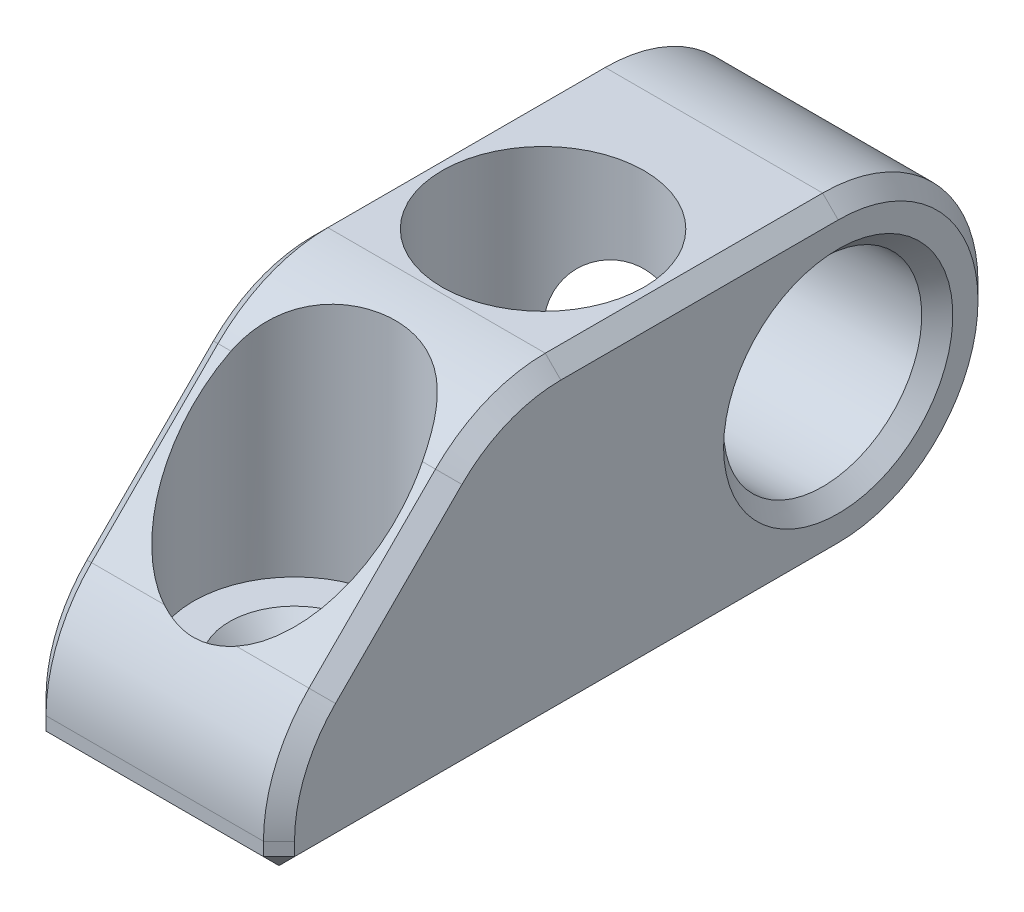
SolidWorks part; units mm, degrees
ref_plane "Front Plane" through (0, 0, 0) normal (0, 0, 1) x (1, 0, 0)
ref_plane "Top Plane" through (0, 0, 0) normal (0, 1, 0) x (1, 0, 0)
ref_plane "Right Plane" through (0, 0, 0) normal (1, 0, 0) x (0, 0, -1)
sketch "Sketch1" plane through (0, 0, 0) normal (0, 1, 0) x (1, 0, 0)
  line L0 (0, 0) -> (0, 1.27) construction
  line L1 (-5.08, -14.605) -> (5.08, -14.605)
  line L2 (-5.08, -14.605) -> (-5.08, 14.605)
  line L3 (-5.08, 14.605) -> (5.08, 14.605)
  line L4 (5.08, -14.605) -> (5.08, 14.605)
  line L5 (-5.08, -14.605) -> (5.08, 14.605) construction
  line L6 (-5.08, 14.605) -> (5.08, -14.605) construction
  line L7 (0, 0) -> (0, -8.89) construction
  circle A0 centre (0, 1.27) radius 2.032
  circle A1 centre (0, -8.89) radius 2.032
  circle A2 centre (0, 1.27) radius 4.1275
  circle A3 centre (0, -8.89) radius 4.1275
  point P0 (0, 0)
  dimension "D3" = 4.064
  dimension "D6" = 8.255
  dimension "D1" = 29.21
  dimension "D2" = 10.16
  dimension "D4" = 8.89
  dimension "D5" = 1.27
extrude "Boss-Extrude1" add sketch "Sketch1" along normal blind 12.7 contours L1 L4 L3 L2 A1 A0 | A1 | A0 | A2 A0 | A3 A1 region at (-4.7707, 0, 0) region at (0, 0, -1.27) region at (0, 0, 8.89) region at (-4.0108, 0, -1.27) region at (-4.0108, 0, 8.89)
sketch "Sketch2" plane through (-5.08, 0, 0) normal (-1, 0, 0) x (0, 0, 1)
  line L0 (-8.255, 0) -> (-8.255, 6.35) construction
  line L1 (14.605, 0) -> (-14.605, 0) construction
  circle A0 centre (-8.255, 6.35) radius 4.05
  dimension "D1" = 8.1
  dimension "D2" = 6.35
  dimension "D3" = 22.86
extrude "Cut-Extrude1" cut sketch "Sketch2" against normal through all contours A0
extrude "Cut-Extrude2" cut sketch "Sketch1<3>" along normal through all contours A0 | A1 region at (0, 0, -1.27) region at (0, 0, 8.89)
sketch "Sketch1<3>" plane through (0, 0, 0) normal (0, 1, 0) x (1, 0, 0) same geometry as "Sketch1"
extrude "Cut-Extrude3" cut sketch "Sketch1<4>" against normal blind 10.16 from surface contours A3 A1 | A2 A0 region at (-4.0108, 0, -1.27) region at (-4.0108, 0, 8.89) starting at face at (0, 12.7, 0.762)
sketch "Sketch1<4>" plane through (0, 0, 0) normal (0, 1, 0) x (1, 0, 0) same geometry as "Sketch1"
chamfer "Chamfer1" distance 8.89 angle 45 1 edges at (0, 12.7, 14.605)
fillet "Fillet1" radius 6.35 3 edges at (0, 3.81, 14.605) (-3.8587, 12.7, 5.715) (3.8587, 12.7, 5.715)
fillet "Fillet2" radius 6.35 2 edges at (0, 12.7, -14.605) (0, 0, -14.605)
chamfer "Chamfer2" distance 0.635 angle 45 2 edges at (-5.08, 6.35, -4.205) (5.08, 6.35, -4.205)
chamfer "Chamfer3" distance 0.635 angle 45 2 edges at (0, 0, 10.922) (0, 0, 0.762)
chamfer "Chamfer4" distance 0.635 angle 45 17 edges at (5.08, 0.5899, 14.605) (-5.08, 0.5899, 14.605) (5.08, 3.6098, 14.1216) (-5.08, 3.6098, 14.1216) (5.08, 8.255, 10.16) (-5.08, 8.255, 10.16) (5.08, 12.2166, 5.5148) (-5.08, 12.2166, 5.5148) (5.08, 12.7, -2.5851) (-5.08, 12.7, -2.5851) (0, 0, 14.605) (-5.08, 0, 3.175) (5.08, 0, 3.175) (-5.08, 10.8401, -12.7451) (5.08, 10.8401, -12.7451) (-5.08, 1.8599, -12.7451) (5.08, 1.8599, -12.7451)
chamfer "Chamfer5" distance 0.635 angle 45 2 edges at (0, 2.54, 0.762) (0, 2.54, 10.922)
